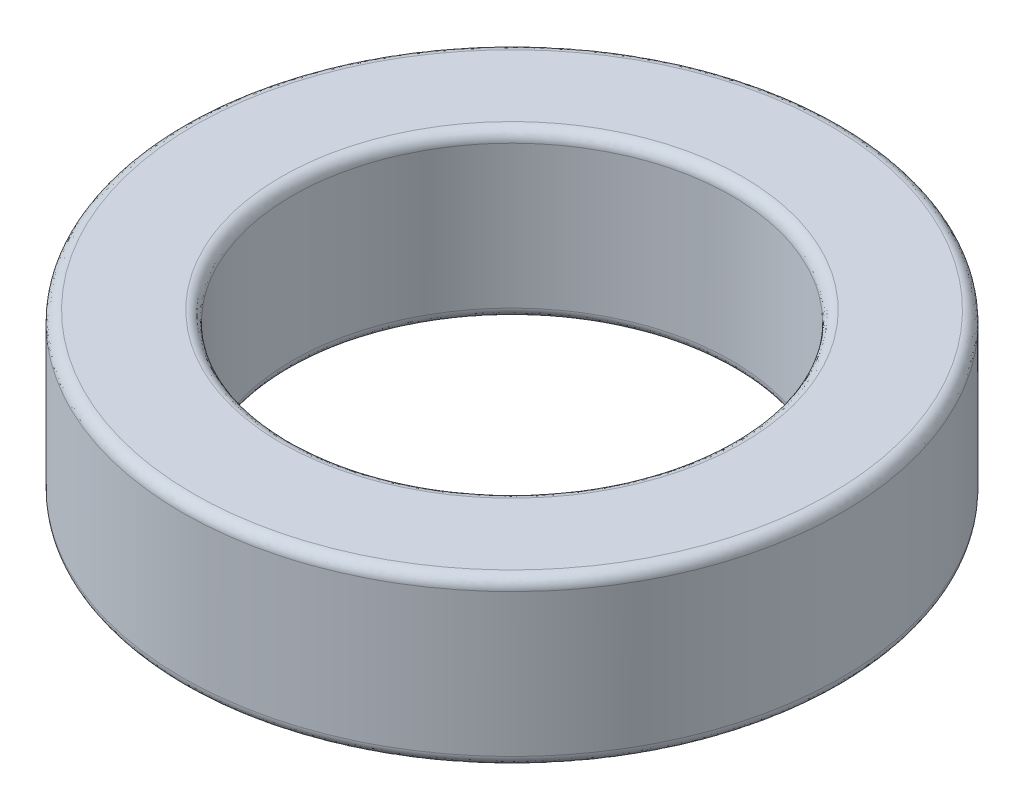
SolidWorks part; units mm, degrees
ref_plane "Front Plane" through (0, 0, 0) normal (0, 0, 1) x (1, 0, 0)
ref_plane "Top Plane" through (0, 0, 0) normal (0, 1, 0) x (1, 0, 0)
ref_plane "Right Plane" through (0, 0, 0) normal (1, 0, 0) x (0, 0, -1)
other "Configuration Table"
sketch "Sketch1" plane through (0, 0, 0) normal (0, 1, 0) x (1, 0, 0)
  circle A0 centre (0, 0) radius 30
  circle A1 centre (0, 0) radius 20
extrude "Boss-Extrude1" add sketch "Sketch1" along normal blind 15
fillet "Fillet1" radius 1 4 edges at (0, 0, 30) (0, 15, 30) (0, 0, 20) (0, 15, 20) first distance on face at (0, 0, 30) first distance on face at (0, 15, 30)
